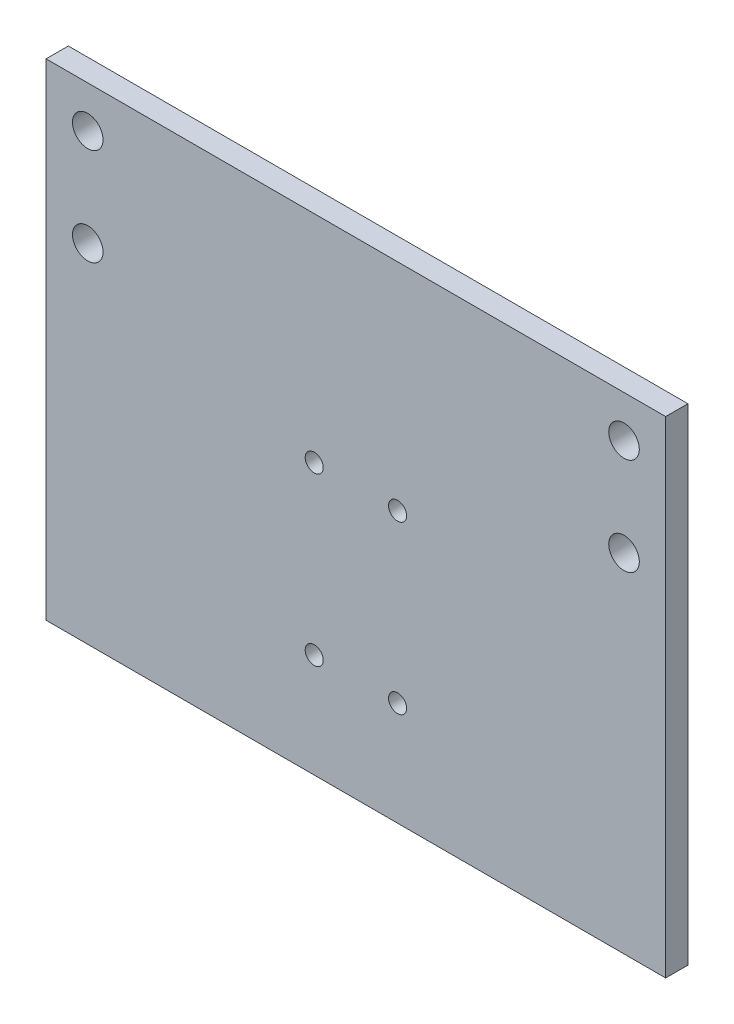
SolidWorks part; units mm, degrees
ref_plane "Front Plane" through (0, 0, 0) normal (0, 0, 1) x (1, 0, 0)
ref_plane "Top Plane" through (0, 0, 0) normal (0, 1, 0) x (1, 0, 0)
ref_plane "Right Plane" through (0, 0, 0) normal (1, 0, 0) x (0, 0, -1)
sketch "Sketch1" plane through (0, 0, 0) normal (0, 0, 1) x (1, 0, 0)
  line L0 (0, -87.5) -> (0, -50.1) construction
  line L1 (-111.5, -87.5) -> (111.5, -87.5)
  line L2 (-111.5, -87.5) -> (-111.5, 87.5)
  line L3 (-111.5, 87.5) -> (111.5, 87.5)
  line L4 (111.5, -87.5) -> (111.5, 87.5)
  line L5 (-111.5, -87.5) -> (111.5, 87.5) construction
  line L6 (-111.5, 87.5) -> (111.5, -87.5) construction
  line L7 (-15, -50.1) -> (15, -50.1) construction
  line L8 (-15, -50.1) -> (-15, 9.9) construction
  line L9 (-15, 9.9) -> (15, 9.9) construction
  line L10 (15, -50.1) -> (15, 9.9) construction
  circle A0 centre (15, 9.9) radius 3.25
  circle A1 centre (-15, 9.9) radius 3.25
  circle A2 centre (-15, -50.1) radius 3.25
  circle A3 centre (15, -50.1) radius 3.25
  point P0 (0, 0)
  dimension "D5" = 6.5
  dimension "D1" = 175
  dimension "D2" = 30
  dimension "D3" = 60
  dimension "D4" = 37.4
  dimension "D6" = 223
base flange "Base-Flange1" sketch "Sketch1" thickness 8 reverse thickness direction no parameters "D1"=2
sketch "Sketch2" plane through (0, 0, 0) normal (0, 0, 1) x (1, 0, 0)
  line L0 (-96.5, 87.5) -> (-96.5, 72.5) construction
  line L1 (111.5, 87.5) -> (-111.5, 87.5) construction
  line L2 (-96.5, 72.5) -> (-96.5, 37.5) construction
  line L3 (0, 0) -> (0, 126.2898) construction
  line L4 (-111.5, 87.5) -> (-111.5, -87.5) construction
  circle A0 centre (-96.5, 72.5) radius 5.5
  circle A1 centre (-96.5, 37.5) radius 5.5
  circle A2 centre (96.5, 37.5) radius 5.5
  circle A3 centre (96.5, 72.5) radius 5.5
  dimension "D4" = 11
  dimension "D1" = 15
  dimension "D2" = 35
  dimension "D3" = 15
extrude "Cut-Extrude1" cut sketch "Sketch2" against normal through all
sketch "Bend-Lines1" [suppressed] plane through (0, 0, 0) normal (0, 1, 0) x (1, 0, 0)
sketch "Bounding-Box1" [suppressed] plane through (0, 0, 0) normal (0, 1, 0) x (1, 0, 0)
sheet metal parameters "Sheet-Metal1" thickness 8 parameters "D1"=2
flat pattern "Flat-Pattern1" [suppressed]
sketch "Bend-Lines2" plane through (0, 0, 0) normal (0, 1, 0) x (1, 0, 0)
sketch3d "Bounding-Box2" [suppressed]
  line L0 (-111.5, -87.5, 0) -> (111.5, -87.5, 0) construction
  line L1 (-111.5, 87.5, 0) -> (111.5, 87.5, 0) construction
  line L2 (-111.5, -87.5, 0) -> (-111.5, 87.5, 0) construction
  line L3 (111.5, -87.5, 0) -> (111.5, 87.5, 0) construction
sheet metal parameters "Sheet-Metal2" thickness 8 parameters "D1"=2
flat pattern "Flat-Pattern1"
sketch "Bend-Lines2" plane through (0, 0, 0) normal (0, 1, 0) x (1, 0, 0)
sketch3d "Bounding-Box2" [suppressed]
  line L0 (-111.5, -87.5, 0) -> (111.5, -87.5, 0) construction
  line L1 (-111.5, 87.5, 0) -> (111.5, 87.5, 0) construction
  line L2 (-111.5, -87.5, 0) -> (-111.5, 87.5, 0) construction
  line L3 (111.5, -87.5, 0) -> (111.5, 87.5, 0) construction
